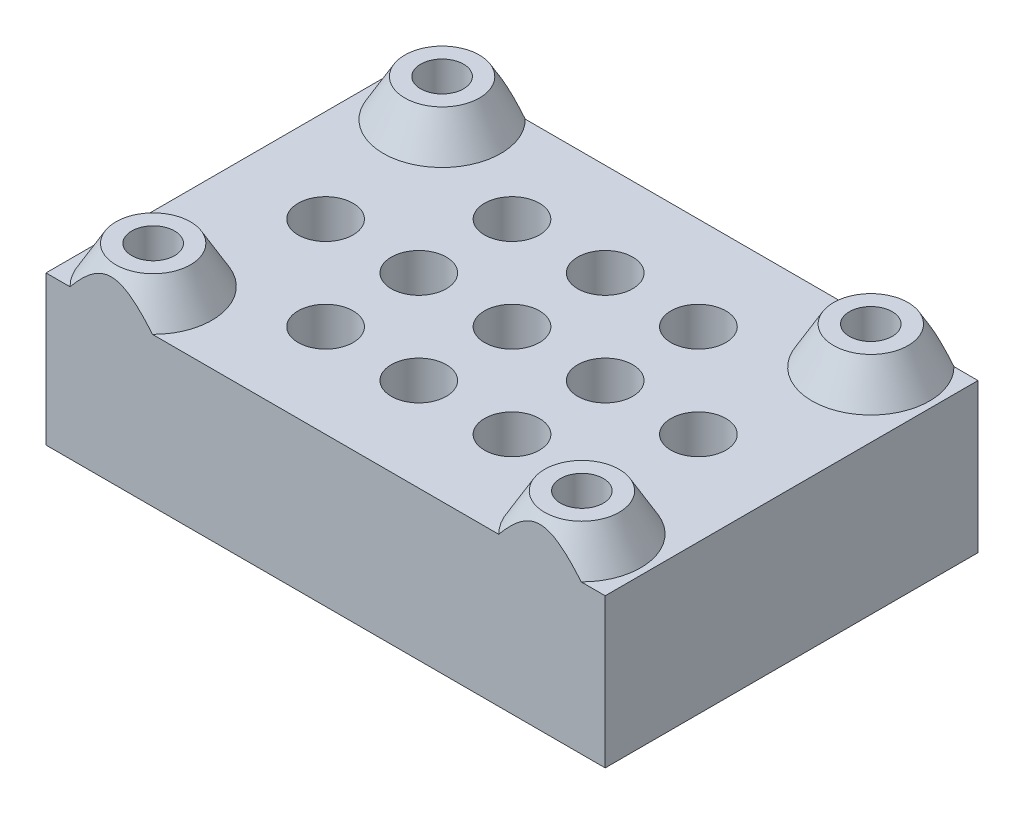
SolidWorks part; units mm, degrees
ref_plane "Front Plane" through (0, 0, 0) normal (0, 0, 1) x (1, 0, 0)
ref_plane "Top Plane" through (0, 0, 0) normal (0, 1, 0) x (1, 0, 0)
ref_plane "Right Plane" through (0, 0, 0) normal (1, 0, 0) x (0, 0, -1)
sketch "Sketch1" plane through (0, 0, 0) normal (0, 1, 0) x (1, 0, 0)
  line L1 (-15, 10) -> (15, 10)
  line L2 (-15, 10) -> (-15, -10)
  line L3 (-15, -10) -> (15, -10)
  line L4 (15, 10) -> (15, -10)
  line L5 (-15, 10) -> (15, -10) construction
  line L6 (-15, -10) -> (15, 10) construction
  point P0 (0, 0)
  dimension "D1" = 30
  dimension "D2" = 20
extrude "Boss-Extrude1" add sketch "Sketch1" along normal blind 8
sketch "Sketch2" plane through (0, 8, 0) normal (0, 1, 0) x (1, 0, 0)
  line L1 (11.5, -7.75) -> (-11.5, -7.75) construction
  line L2 (11.5, -7.75) -> (11.5, 7.75) construction
  line L3 (11.5, 7.75) -> (-11.5, 7.75) construction
  line L4 (-11.5, -7.75) -> (-11.5, 7.75) construction
  line L5 (11.5, -7.75) -> (-11.5, 7.75) construction
  line L6 (11.5, 7.75) -> (-11.5, -7.75) construction
  circle A0 centre (-11.5, 7.75) radius 0.95
  circle A1 centre (-11.5, -7.75) radius 0.95
  circle A2 centre (11.5, -7.75) radius 0.95
  circle A3 centre (11.5, 7.75) radius 0.95
  point P0 (0, 0)
  dimension "D1" = 1.9
  dimension "D2" = 15.5
  dimension "D3" = 23
extrude "Cut-Extrude1" cut sketch "Sketch2" against normal through all
sketch "Sketch3" plane through (0, 8, 0) normal (0, 1, 0) x (1, 0, 0)
  circle A0 centre (-11.5, -7.75) radius 2
  circle A1 centre (-11.5, 7.75) radius 2
  circle A2 centre (11.5, 7.75) radius 2
  circle A3 centre (11.5, -7.75) radius 2
  circle A4 centre (11.5, -7.75) radius 0.95 construction
  circle A5 centre (11.5, 7.75) radius 0.95 construction
  circle A6 centre (-11.5, 7.75) radius 0.95 construction
  circle A7 centre (-11.5, -7.75) radius 0.95 construction
  circle A8 centre (11.5, -7.75) radius 0.95
  circle A9 centre (11.5, 7.75) radius 0.95
  circle A10 centre (-11.5, 7.75) radius 0.95
  circle A11 centre (-11.5, -7.75) radius 0.95
  dimension "D1" = 4
extrude "Boss-Extrude2" add sketch "Sketch3" along normal blind 2
chamfer "Chamfer1" distance 2 angle 30 4 edges at (11.5, 8, -5.75) (11.5, 8, 9.75) (-11.5, 8, 9.75) (-11.5, 8, -5.75) first distance on face at (11.5, 10, -5.75) first distance on face at (11.5, 10, 9.75) first distance on face at (-11.5, 10, 9.75) first distance on face at (-11.5, 10, -5.75)
sketch "Sketch4" plane through (0, 0, 0) normal (0, -1, 0) x (1, 0, 0)
  circle A0 centre (-10, 0) radius 1.475
  dimension "D1" = 2.95
  dimension "D2" = 10
extrude "Cut-Extrude2" cut sketch "Sketch4" against normal through all
pattern_linear "LPattern1" count 5 spacing 5 along (1, 0, 0) count 2 spacing 5 along (0, 0, 1) skipping (0, 1), (4, 1) of "Cut-Extrude2"
mirror "Mirror1" about plane through (0, 0, 0) normal (0, 0, 1) of "LPattern1"
sketch "Sketch5" plane through (0, 10, 0) normal (0, 1, 0) x (1, 0, 0)
  circle A0 centre (-11.5, 7.75) radius 1.15
  circle A1 centre (-11.5, -7.75) radius 1.15
  circle A2 centre (11.5, 7.75) radius 1.15
  circle A3 centre (11.5, -7.75) radius 1.15
  dimension "D1" = 2.3
extrude "Cut-Extrude3" cut sketch "Sketch5" against normal blind 2
